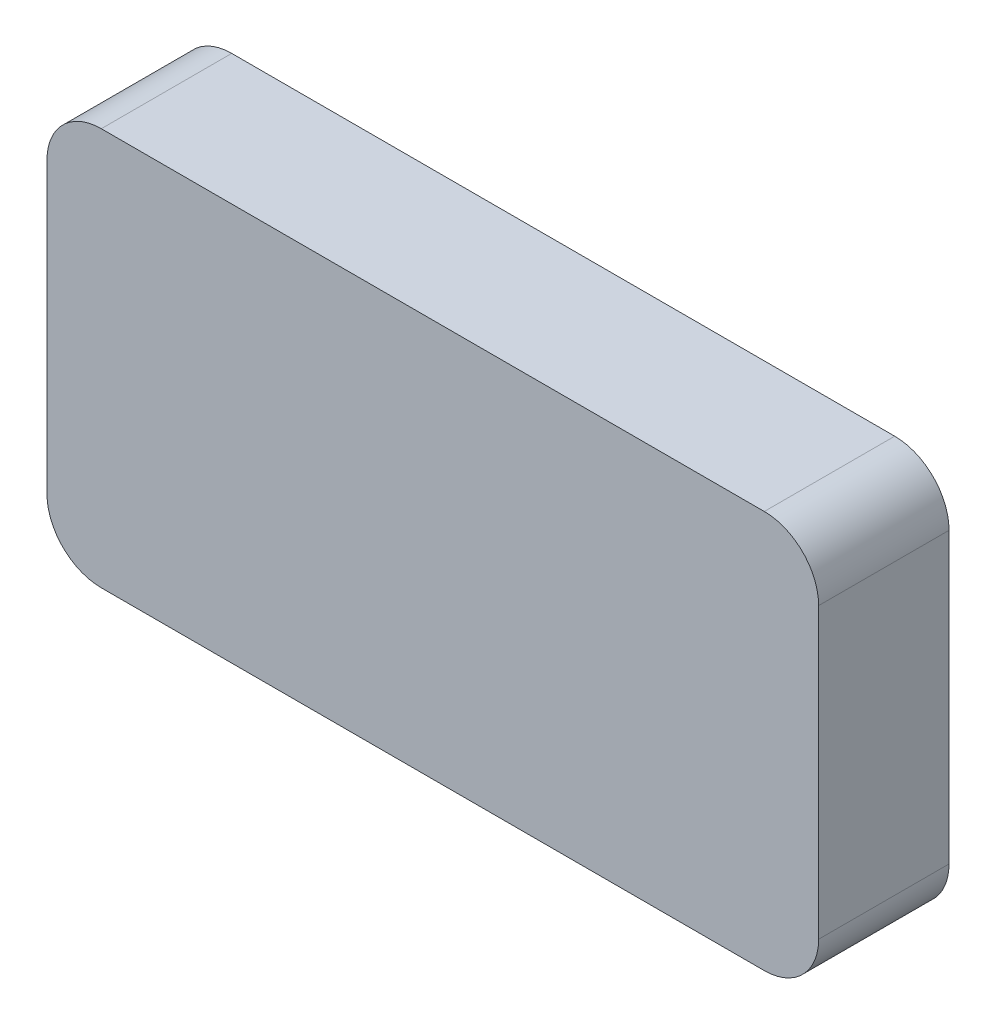
SolidWorks part; units mm, degrees
ref_plane "Plan de face" through (0, 0, 0) normal (0, 0, 1) x (1, 0, 0)
ref_plane "Plan de dessus" through (0, 0, 0) normal (0, 1, 0) x (1, 0, 0)
ref_plane "Plan de droite" through (0, 0, 0) normal (1, 0, 0) x (0, 0, -1)
sketch "Sketch2" plane through (0, 0, 0) normal (0, 0, 1) x (1, 0, 0)
  line L1 (21.3, -10.975) -> (-21.3, -10.975)
  line L2 (21.3, -10.975) -> (21.3, 10.975)
  line L3 (21.3, 10.975) -> (-21.3, 10.975)
  line L4 (-21.3, -10.975) -> (-21.3, 10.975)
  line L5 (21.3, -10.975) -> (-21.3, 10.975) construction
  line L6 (21.3, 10.975) -> (-21.3, -10.975) construction
  point P0 (0, 0)
  dimension "D1" = 42.6
  dimension "D2" = 21.95
extrude "Boss-Extrude1" add sketch "Sketch2" along normal blind 7.2
fillet "Fillet1" radius 3 4 edges at (-21.3, -10.975, 3.6) (21.3, -10.975, 3.6) (21.3, 10.975, 3.6) (-21.3, 10.975, 3.6)
